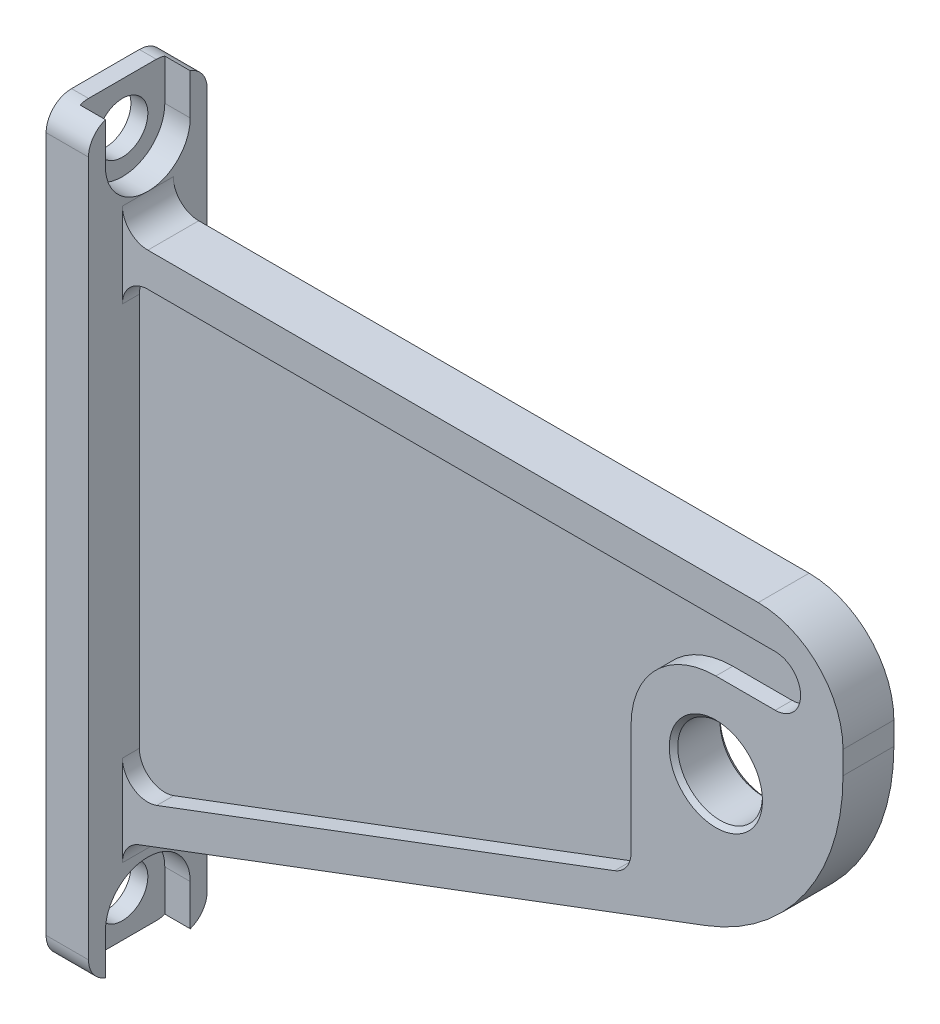
SolidWorks part; units mm, degrees
ref_plane "Спереди" through (0, 0, 0) normal (0, 0, 1) x (1, 0, 0)
ref_plane "Сверху" through (0, 0, 0) normal (0, 1, 0) x (1, 0, 0)
ref_plane "Справа" through (0, 0, 0) normal (1, 0, 0) x (0, 0, -1)
sketch "Эскиз2" plane through (0, 0, 0) normal (0, 0, 1) x (1, 0, 0)
  line L0 (75, 65) -> (82, 65)
  line L5 (0, 0) -> (5, 0)
  line L6 (0, 0) -> (0, 88)
  line L7 (0, 88) -> (5, 88)
  line L8 (5, 0) -> (5, 10.924)
  line L9 (8, 75) -> (80, 75)
  line L11 (8, 71) -> (82, 71)
  line L13 (9.0571, 18.8018) -> (63.0571, 39.1346)
  line L15 (6.9429, 13.7315) -> (73.8095, 38.909)
  line L18 (65, 55) -> (65, 41.9421)
  line L19 (90, 65) -> (90, 62.3055)
  line L21 (5, 21.6094) -> (5, 68)
  line L22 (5, 78) -> (5, 88)
  line L23 (5, 78) -> (5, 68)
  line L24 (5, 21.6094) -> (5, 10.924)
  arc A0 (75, 65) -> (65, 55) centre (75, 55) ccw
  arc A1 (82, 71) -> (82, 65) centre (82, 68) cw
  arc A2 (73.8095, 38.909) -> (90, 62.3055) centre (65, 62.3055) ccw
  arc A3 (90, 65) -> (80, 75) centre (80, 65) ccw
  arc A7 (63.0571, 39.1346) -> (65, 41.9421) centre (62, 41.9421) ccw
  arc A8 (5, 10.924) -> (6.9429, 13.7315) centre (8, 10.924) cw
  arc A9 (9.0571, 18.8018) -> (5, 21.6094) centre (8, 21.6094) cw
  arc A10 (5, 68) -> (8, 71) centre (8, 68) cw
  arc A11 (8, 75) -> (5, 78) centre (8, 78) cw
  circle A12 centre (75, 55) radius 5
  point P24 (5, 13)
  point P29 (5, 17.2742)
  point P31 (85, 68)
  point P35 (5, 75)
  dimension "D5" = 10
  dimension "D7" = 25
  dimension "D8" = 10
  dimension "D18" = 3
  dimension "D19" = 10
  dimension "D3" = 110.633
  dimension "D1" = 5
  dimension "D2" = 88
  dimension "D4" = 65
  dimension "D6" = 75
  dimension "D9" = 80
  dimension "D10" = 75
  dimension "D11" = 71
  dimension "D12" = 85
  dimension "D13" = 65
  dimension "D14" = 55
  dimension "D15" = 13
  dimension "D16" = 4
  dimension "D17" = 90
extrude "Бобышка-Вытянуть2" add sketch "Эскиз2" along normal mid plane 14 contours L24 L21 L23 L22 L7 L6 L5 L8 region at (2.5, 44, 0)
extrude "Бобышка-Вытянуть6" add sketch "Эскиз2<10>" along normal mid plane 6 contours L9 A11 L23 A10 L11 A1 L0 A0 L18 A7 L13 A9 L24 A8 L15 A2 L19 A3 A12 region at (78.5, 63.9172, 0)
sketch "Эскиз2<10>" plane through (0, 0, 0) normal (0, 0, 1) x (1, 0, 0) same geometry as "Эскиз2"
extrude "Бобышка-Вытянуть7" add sketch "Эскиз2<11>" along normal mid plane 2 contours A10 L21 A9 L13 A7 L18 A0 L0 A1 L11 region at (34.5077, 50.241, 0)
sketch "Эскиз2<11>" plane through (0, 0, 0) normal (0, 0, 1) x (1, 0, 0) same geometry as "Эскиз2"
sketch "Эскиз5" plane through (5, 0, 0) normal (1, 0, 0) x (0, 0, -1)
  line L0 (0, 0) -> (0, 6.2811) construction
  line L1 (-7, 88) -> (7, 88) construction
  line L2 (-5, 83) -> (-5, 88)
  line L3 (5, 83) -> (5, 88)
  line L4 (-5, 5) -> (-5, 0)
  line L5 (-7, 0) -> (7, 0) construction
  line L6 (5, 5) -> (5, 0)
  arc A0 (-5, 83) -> (5, 83) centre (0, 83) ccw
  circle A1 centre (0, 83) radius 3
  arc A2 (5, 5) -> (-5, 5) centre (0, 5) ccw
  circle A3 centre (0, 5) radius 3
  line M15 (7, 88) -> (-7, 88)
  line M17 (-7, 0) -> (7, 0)
  dimension "D1" = 5
  dimension "D2" = 5
  dimension "D3" = 3
  dimension "D4" = 5
  dimension "D5" = 3
extrude "Вырез-Вытянуть1" cut sketch "Эскиз5" against normal blind 3 contours L0 A0 L3 A1 M15 | A0 L0 A1 L2 M15 | L0 A3 A2 L4 M17 | L0 L6 A2 A3 M17 region at (5, 0.1414, 2.5) region at (5, 85.5, 4.8586)
extrude "Вырез-Вытянуть2" cut sketch "Эскиз5<5>" against normal through all contours A3 L0 | L0 A3 | L0 A1 | A1 L0 region at (5, 83, 0) region at (5, 2.9387, -2.0613)
sketch "Эскиз5<5>" plane through (5, 0, 0) normal (1, 0, 0) x (0, 0, -1) same geometry as "Эскиз5"
fillet "Скругление1" radius 3 4 edges at (2.5, 0, 7) (2.5, 0, -7) (2.5, 88, -7) (2.5, 88, 7)
chamfer "Фаска2" distance 0.5 angle 45 2 edges at (80, 55, -3) (80, 55, 3)
equation "\"r_s\"= 3"
equation "\"D18@Эскиз2\"=\"r_s\""
